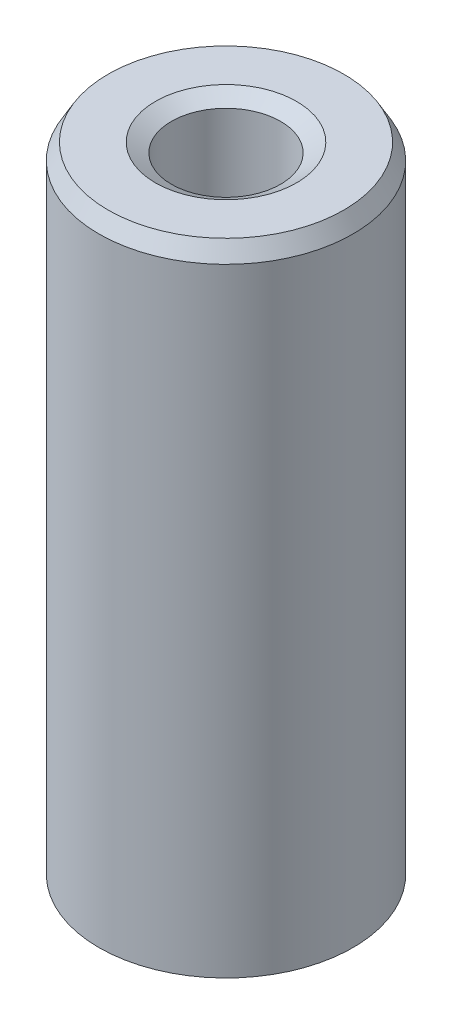
SolidWorks part; units mm, degrees
ref_plane "Front Plane" through (0, 0, 0) normal (0, 0, 1) x (1, 0, 0)
ref_plane "Top Plane" through (0, 0, 0) normal (0, 1, 0) x (1, 0, 0)
ref_plane "Right Plane" through (0, 0, 0) normal (1, 0, 0) x (0, 0, -1)
sketch "Sketch1" plane through (0, 0, 0) normal (0, 1, 0) x (1, 0, 0)
  circle A0 centre (0, 0) radius 20
  dimension "SLEEVE_OD" = 40
extrude "Boss-Extrude1" add sketch "Sketch1" along normal blind 101.2586
sketch "Sketch2" plane through (0, 0, 0) normal (0, 1, 0) x (1, 0, 0)
  circle A0 centre (0, 0) radius 8.5895
  dimension "BORE_D" = 17.179
extrude "Cut-Extrude1" cut sketch "Sketch2" along normal through all
chamfer "Chamfer1" distance 2.5233 angle 30 4 edges at (0, 101.2586, 8.5895) (0, 0, 8.5895) (0, 0, 20) (0, 101.2586, 20) first distance on face at (0, 101.2586, 8.5895) first distance on face at (0, 0, 8.5895) first distance on face at (0, 101.2586, 20)
